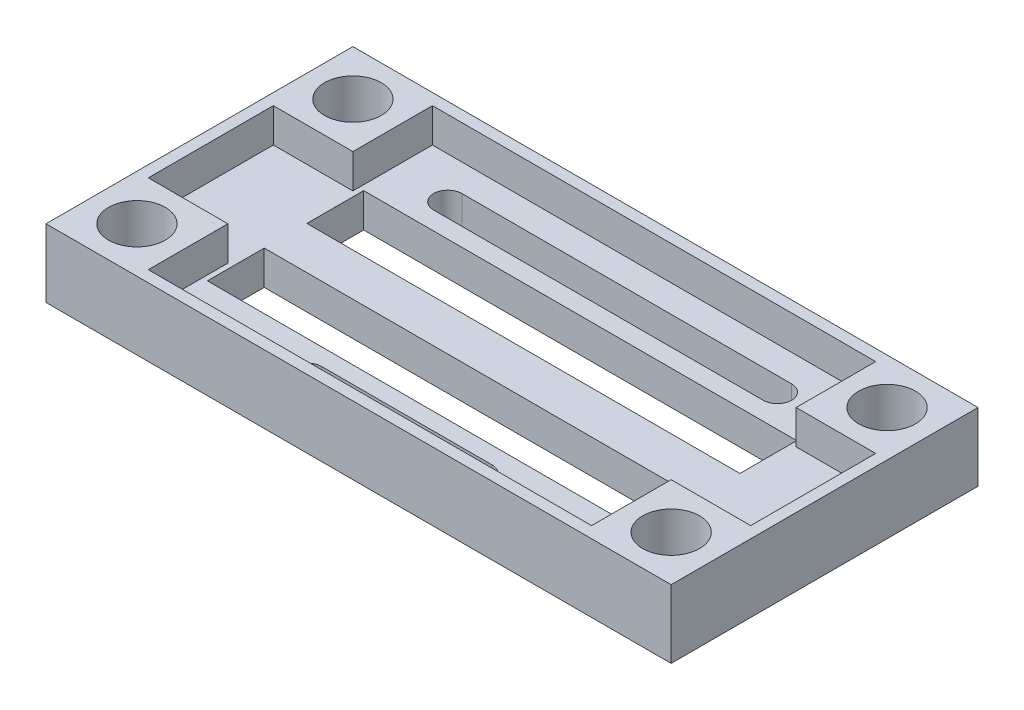
SolidWorks part; units mm, degrees
ref_plane "Front Plane" through (0, 0, 0) normal (0, 0, 1) x (1, 0, 0)
ref_plane "Top Plane" through (0, 0, 0) normal (0, 1, 0) x (1, 0, 0)
ref_plane "Right Plane" through (0, 0, 0) normal (1, 0, 0) x (0, 0, -1)
sketch "Sketch1" plane through (0, 0, 0) normal (0, 1, 0) x (1, 0, 0)
  line L0 (-19.05, -2.75) -> (19.05, -2.75)
  line L9 (27.5, -13.5) -> (-27.5, -13.5)
  line L10 (27.5, -13.5) -> (27.5, 13.5)
  line L11 (27.5, 13.5) -> (-27.5, 13.5)
  line L20 (-27.5, -13.5) -> (-27.5, 13.5)
  line L21 (27.5, -13.5) -> (-27.5, 13.5) construction
  line L22 (27.5, 13.5) -> (-27.5, -13.5) construction
  line L23 (-19.05, 6) -> (19.05, 6)
  line L24 (-19.05, 6) -> (-19.05, 1)
  line L25 (-19.05, 1) -> (19.05, 1)
  line L26 (19.05, 6) -> (19.05, 1)
  line L27 (-19.05, -2.75) -> (-19.05, -7.75)
  line L28 (-19.05, -7.75) -> (19.05, -7.75)
  line L29 (19.05, -2.75) -> (19.05, -7.75)
  point P0 (0, 0)
  point P10 (0, 6)
  point P11 (0, 13.5)
  point P15 (0, -2.75)
  point P16 (-13.8058, -9)
  dimension "D2" = 55
  dimension "D1" = 27
  dimension "D3" = 38.1
  dimension "D4" = 7.5
  dimension "D5" = 5
  dimension "D6" = 3.75
extrude "Bottom Base" add sketch "Sketch1" along normal blind 3
sketch "Sketch3" plane through (0, 3, 0) normal (0, 1, 0) x (1, 0, 0)
  line L0 (-27.5, 8.85) -> (27.5, 8.85) construction
  line L1 (27.5, 13.5) -> (-27.5, 13.5) construction
  line L3 (-14.5, 10.1) -> (14.5, 10.1) construction
  line L4 (19.05, 6) -> (-19.05, 6) construction
  line L5 (-14.5, 8.85) -> (14.5, 8.85) construction
  line L6 (-14.5, 10.1) -> (14.5, 10.1)
  line L7 (-14.5, 7.6) -> (14.5, 7.6)
  line L8 (-27.5, 13.5) -> (-27.5, -13.5) construction
  line L9 (27.5, -13.5) -> (27.5, 13.5) construction
  circle A0 centre (-14.5, 8.85) radius 1.09 construction
  circle A2 centre (-14.5, 8.85) radius 1.25 construction
  circle A3 centre (14.5, 8.85) radius 1.25 construction
  arc A6 (-14.5, 10.1) -> (-14.5, 7.6) centre (-14.5, 8.85) ccw
  arc A7 (14.5, 7.6) -> (14.5, 10.1) centre (14.5, 8.85) ccw
  point P2 (-14.5, 9.3078)
  point P11 (-14.5, 8.85)
  point P14 (-14.5, 8.85)
  point P16 (0, 0)
  point P17 (-0.2069, 8.85)
  point P21 (0, 6)
  point P22 (0, 10.1)
  point P25 (0, 8.85)
  point P32 (-14.033, 6.6864)
  point P33 (-14.236, 8.85)
  dimension "D2" = 2.5
  dimension "D5" = 1.25
  dimension "D1" = 29
  dimension "D6" = 4.65
extrude "Sensor Mounting Holes" cut sketch "Sketch3" against normal blind 3
sketch "Sketch4" plane through (0, 3, 0) normal (0, 1, 0) x (1, 0, 0)
  line L0 (27.5, -13.5) -> (27.5, 13.5) construction
  line L1 (27.5, 13.5) -> (-27.5, 13.5) construction
  line L2 (-27.5, -13.5) -> (27.5, -13.5) construction
  line L3 (-27.5, 13.5) -> (-27.5, -13.5) construction
  line L4 (27.5, -13.5) -> (27.5, 13.5)
  line L5 (27.5, 13.5) -> (-27.5, 13.5)
  line L6 (-27.5, -13.5) -> (27.5, -13.5)
  line L7 (-27.5, 13.5) -> (-27.5, -13.5)
  line L8 (26.5, -12.5) -> (26.5, 12.5)
  line L9 (26.5, 12.5) -> (-26.5, 12.5)
  line L10 (-26.5, 12.5) -> (-26.5, -12.5)
  line L11 (-26.5, -12.5) -> (26.5, -12.5)
  line L12 (0, -13.5) -> (0, 13.5) construction
  line L13 (-26.5, -12.5) -> (-19.5, -12.5)
  line L14 (-26.5, -12.5) -> (-26.5, -5.5)
  line L15 (-26.5, -5.5) -> (-19.5, -5.5)
  line L16 (-19.5, -12.5) -> (-19.5, -5.5)
  line L29 (27.5, 0) -> (-27.5, 0) construction
  line L30 (26.5, -5.5) -> (19.5, -5.5)
  line L31 (19.5, -12.5) -> (19.5, -5.5)
  line L32 (26.5, -12.5) -> (19.5, -12.5)
  line L33 (26.5, -12.5) -> (26.5, -5.5)
  line L34 (26.5, 12.5) -> (19.5, 12.5)
  line L35 (19.5, 12.5) -> (19.5, 5.5)
  line L36 (26.5, 5.5) -> (19.5, 5.5)
  line L37 (26.5, 12.5) -> (26.5, 5.5)
  line L38 (-26.5, 5.5) -> (-19.5, 5.5)
  line L39 (-19.5, 12.5) -> (-19.5, 5.5)
  line L40 (-26.5, 12.5) -> (-19.5, 12.5)
  line L41 (-26.5, 12.5) -> (-26.5, 5.5)
  point P14 (0, 0)
  point P17 (0, 0)
  line M13 (-27.5, 13.5) -> (-27.5, -13.5)
  line M14 (-27.5, -13.5) -> (27.5, -13.5)
  line M15 (27.5, -13.5) -> (27.5, 13.5)
  line M16 (27.5, 13.5) -> (-27.5, 13.5)
  dimension "D2" = 7
  dimension "D1" = 1
extrude "Outer Rim" add sketch "Sketch4" along normal blind 3 contours L39 L9 L10 L38 | L11 L16 L15 L10 | L31 L11 L8 L30 | L36 L8 L9 L35 | L11 L10 L9 L8 M16 M13 M14 M15 region at (0, 3, 12.8873) region at (23, 3, 9) region at (23, 3, -9) region at (-23, 3, 9) region at (-23, 3, -9)
sketch "Sketch6" plane through (0, 6, 0) normal (0, 1, 0) x (1, 0, 0)
  line L0 (-26.5, -5.5) -> (-19.5, -5.5) construction
  line L1 (-19.5, 5.5) -> (-27.5, 5.5) construction
  line L2 (-19.5, 5.5) -> (-19.5, 13.5) construction
  line L3 (-19.5, 13.5) -> (-27.5, 13.5) construction
  line L4 (-27.5, 5.5) -> (-27.5, 13.5) construction
  line L5 (-19.5, 5.5) -> (-27.5, 13.5) construction
  line L6 (-19.5, 13.5) -> (-27.5, 5.5) construction
  line L7 (-19.5, -13.5) -> (-27.5, -13.5) construction
  line L8 (-19.5, -13.5) -> (-19.5, -5.5) construction
  line L9 (-19.5, -5.5) -> (-27.5, -5.5) construction
  line L10 (-27.5, -13.5) -> (-27.5, -5.5) construction
  line L11 (-19.5, -13.5) -> (-27.5, -5.5) construction
  line L12 (-19.5, -5.5) -> (-27.5, -13.5) construction
  line L17 (-26.5, -5.5) -> (-19.5, -5.5) construction
  line L18 (19.5, -12.5) -> (19.5, -5.5) construction
  line L23 (27.5, 5.5) -> (19.5, 5.5) construction
  line L24 (27.5, 5.5) -> (27.5, 13.5) construction
  line L25 (27.5, 13.5) -> (19.5, 13.5) construction
  line L26 (19.5, 5.5) -> (19.5, 13.5) construction
  line L27 (27.5, 5.5) -> (19.5, 13.5) construction
  line L28 (27.5, 13.5) -> (19.5, 5.5) construction
  line L29 (27.5, -13.5) -> (19.5, -13.5) construction
  line L30 (27.5, -13.5) -> (27.5, -5.5) construction
  line L31 (27.5, -5.5) -> (19.5, -5.5) construction
  line L32 (19.5, -13.5) -> (19.5, -5.5) construction
  line L33 (27.5, -13.5) -> (19.5, -5.5) construction
  line L34 (27.5, -5.5) -> (19.5, -13.5) construction
  line L35 (-19.5, -12.5) -> (-19.5, -5.5) construction
  line L36 (-19.5, -12.5) -> (-19.5, -5.5) construction
  line L37 (27.5, -13.5) -> (27.5, 13.5) construction
  point P0 (-23.5, 9.5)
  point P5 (-23.5, -9.5)
  point P10 (23.5, -9.5)
  point P16 (23.5, 9.5)
hole_wizard "M4 bolt holes" positions "Sketch7" profile "Sketch8" hole size "Ø5.0" standard "ANSI Metric" end condition through all
sketch "Sketch7" plane through (0, 6, 0) normal (0, 1, 0) x (1, 0, 0)
  line L0 (-19.5, -13.5) -> (-27.5, -5.5) construction
  point P0 (-23.5, 9.5)
  point P3 (-23.5, -9.5)
  point P7 (23.5, 9.5)
  point P10 (23.5, -9.5)
sketch "Sketch8" plane through (-23.5, 6, -9.5) normal (1, 0, 0) x (0, 0, 1)
  line L0 (0, 0) -> (0, 6)
  line L1 (0, 6) -> (2.5, 6)
  line L2 (2.5, 6) -> (2.5, 0)
  line L5 (2.5, 0) -> (0, 0)
  line L11 (0, -6.35) -> (0, 107.95) construction
  dimension "Thru Hole Dia." = 5
  dimension "Thru Hole Depth" = 6
sketch "Sketch10" plane through (0, 0, 0) normal (0, -1, 0) x (1, 0, 0)
  line L0 (-27.5, -3.5) -> (27.5, -3.5) construction
  line L1 (-27.5, -13.5) -> (-27.5, 13.5) construction
  line L2 (27.5, 13.5) -> (27.5, -13.5) construction
  line L3 (-19.05, -6) -> (-19.05, -1) construction
  point P8 (-19.05, -3.5)
sketch "Sketch11" plane through (0, 3, 0) normal (0, 1, 0) x (1, 0, 0)
  line L0 (-7.5, -10.5) -> (7.5, -10.5) construction
  line L1 (-7.5, -9.25) -> (7.5, -9.25)
  line L2 (-7.5, -11.75) -> (7.5, -11.75)
  line L3 (-19.5, -12.5) -> (19.5, -12.5) construction
  arc A0 (-7.5, -9.25) -> (-7.5, -11.75) centre (-7.5, -10.5) ccw
  arc A1 (7.5, -11.75) -> (7.5, -9.25) centre (7.5, -10.5) ccw
  arc A2 (-14.5, 10.1) -> (-14.5, 7.6) centre (-14.5, 8.85) ccw construction
  point P2 (0, -10.5)
  point P10 (0, 0)
  point P12 (0, -10.5934)
  dimension "D1" = 2
  dimension "D2" = 15
extrude "backwards sensor" cut sketch "Sketch11" against normal up to surface (3 mm away) up to face at (-23.5, 0, -7)
